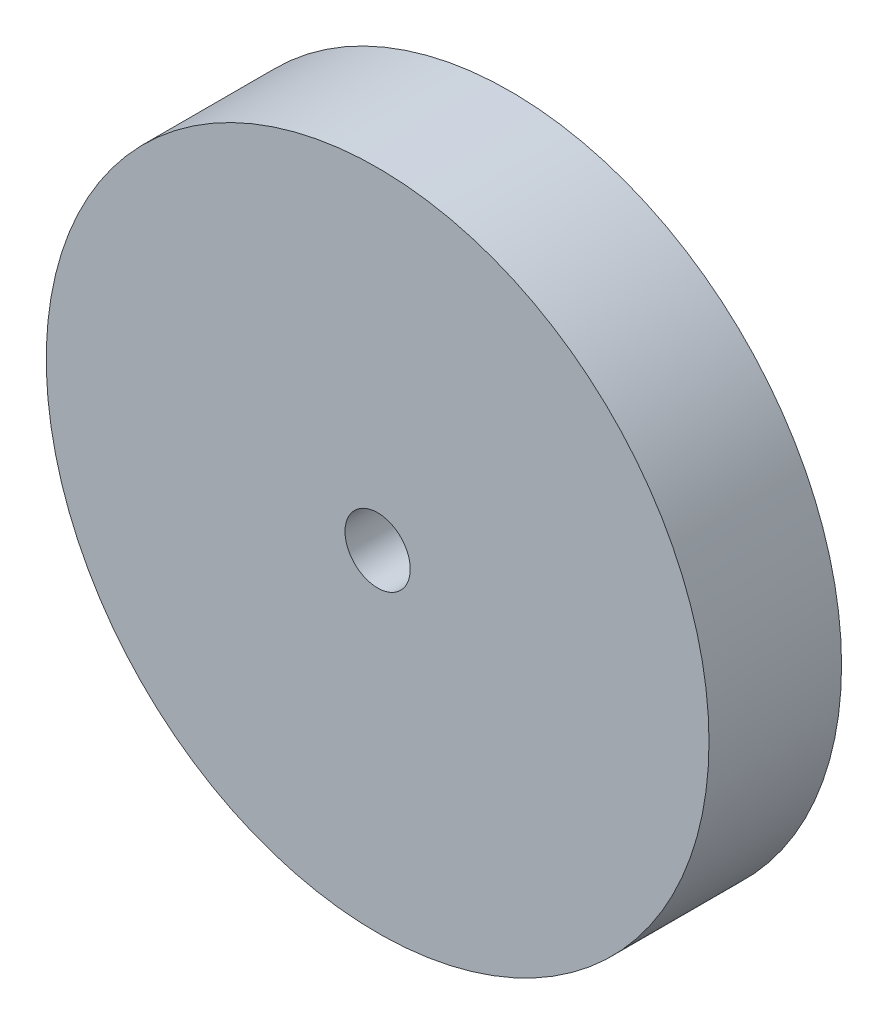
SolidWorks part; units mm, degrees
ref_plane "Front Plane" through (0, 0, 0) normal (0, 0, 1) x (1, 0, 0)
ref_plane "Top Plane" through (0, 0, 0) normal (0, 1, 0) x (1, 0, 0)
ref_plane "Right Plane" through (0, 0, 0) normal (1, 0, 0) x (0, 0, -1)
sketch "Sketch1" plane through (0, 0, 0) normal (0, 0, 1) x (1, 0, 0)
  circle A0 centre (0, 0) radius 127
  dimension "D1" = 254
extrude "Boss-Extrude1" add sketch "Sketch1" along normal blind 50.8
hole_wizard "Ø25.0mm Dowel Hole1" positions "Sketch2" profile "Sketch3" hole size "Ø25.0" standard "DIN" end condition through all
sketch "Sketch2" plane through (0, 0, 0) normal (0, 0, -1) x (-1, 0, 0)
  point P0 (0, 0)
sketch "Sketch3" plane through (0, 0, 0) normal (1, 0, 0) x (0, 1, 0)
  line L0 (0, 0) -> (0, 50.8)
  line L1 (0, 50.8) -> (12.5, 50.8)
  line L2 (12.5, 50.8) -> (12.5, 0)
  line L5 (12.5, 0) -> (0, 0)
  line L11 (0, -6.35) -> (0, 107.95) construction
  dimension "Thru Hole Dia." = 25
  dimension "Thru Hole Depth" = 50.8
